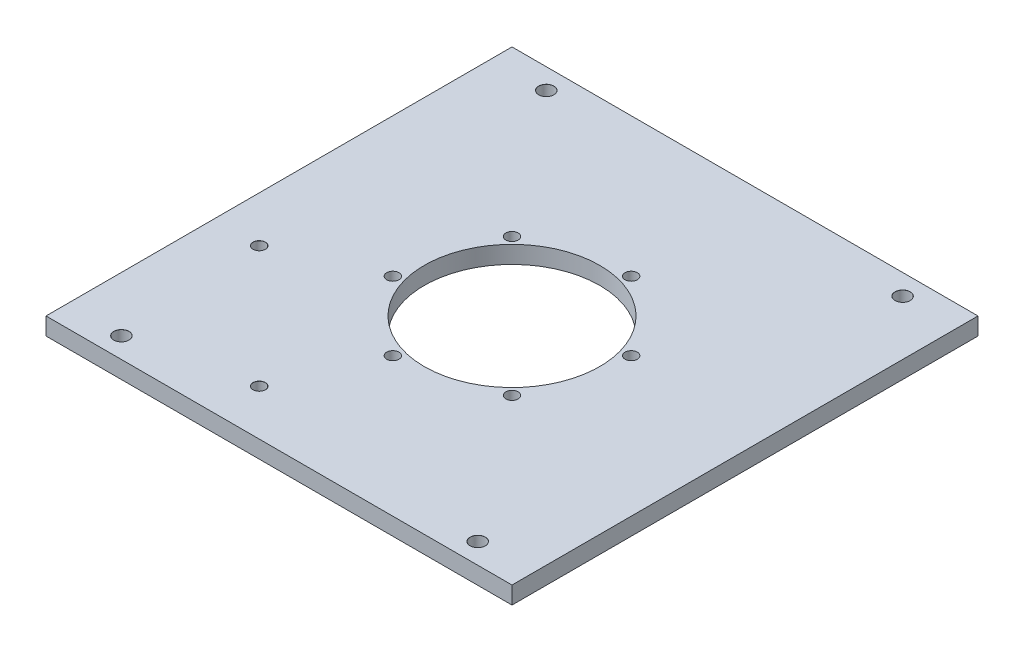
SolidWorks part; units mm, degrees
material "6061 Alloy"
ref_plane "Front Plane" through (0, 0, 0) normal (0, 0, 1) x (1, 0, 0)
ref_plane "Top Plane" through (0, 0, 0) normal (0, 1, 0) x (1, 0, 0)
ref_plane "Right Plane" through (0, 0, 0) normal (1, 0, 0) x (0, 0, -1)
sketch "Sketch1" plane through (0, 0, 0) normal (0, 1, 0) x (1, 0, 0)
  line L1 (-85, -85) -> (85, -85)
  line L2 (-85, -85) -> (-85, 85)
  line L3 (-85, 85) -> (85, 85)
  line L4 (85, -85) -> (85, 85)
  line L5 (-85, -85) -> (85, 85) construction
  line L6 (-85, 85) -> (85, -85) construction
  circle A1 centre (0, 0) radius 39.5
  arc A5 (-25.1023, 25.1023) -> (9.1881, 34.2904) centre (0, 0) cw
  arc A7 (9.1881, 34.2904) -> (-34.2904, -9.1881) centre (0, 0) ccw
  arc A9 (-34.2904, -9.1881) -> (-9.1881, -34.2904) centre (0, 0) ccw
  arc A11 (-9.1881, -34.2904) -> (25.1023, -25.1023) centre (0, 0) ccw
  circle A13 centre (0, 0) radius 32
  arc A14 (25.1023, -25.1023) -> (34.2904, 9.1881) centre (0, 0) ccw
extrude "Boss-Extrude3" add sketch "Sketch1" along normal blind 6.35 contours L1 L4 L3 L2 A1 | A1 A13 region at (-82.5958, 0, 0) region at (-38.3828, 0, 0)
hole_wizard "M4 Clearance Hole2" positions "Sketch6" profile "Sketch7" hole size "M4" standard "ANSI Metric" end condition through all
sketch "Sketch6" plane through (0, 0, 0) normal (0, -1, 0) x (-1, 0, 0)
  point P0 (-9.1881, 34.2904)
  point P3 (25.1023, 25.1023)
  point P6 (34.2904, -9.1881)
  point P9 (9.1881, -34.2904)
  point P12 (-25.1023, -25.1023)
  point P15 (-34.2904, 9.1881)
sketch "Sketch7" plane through (9.1881, 0, -34.2904) normal (1, 0, 0) x (0, 0, -1)
  line L0 (0, 0) -> (0, 6.35)
  line L1 (0, 6.35) -> (2.25, 6.35)
  line L2 (2.25, 6.35) -> (2.25, 0.025)
  line L3 (2.25, 0.025) -> (2.275, 0)
  line L5 (2.275, 0) -> (0, 0)
  line L6 (-2.25, 0.025) -> (-2.275, 0) construction
  line L11 (0, -6.35) -> (0, 107.95) construction
  dimension "Thru Hole Dia." = 4.5
  dimension "Thru Hole Depth" = 6.35
  dimension "Near C'Sink Dia." = 4.55
  dimension "Near C'Sink Angle" = 90
sketch "Sketch13" plane through (0, 6.35, 0) normal (0, 1, 0) x (1, 0, 0)
  line L0 (-85, -85) -> (-46.1091, -46.1091)
  line L1 (-46.1091, -46.1091) -> (-68.3017, -23.9166)
  line L2 (-46.1091, -46.1091) -> (-23.9166, -68.3017)
hole_wizard "M4 Clearance Hole5" positions "Sketch14" profile "Sketch15" hole size "M4" standard "ANSI Metric" end condition through all
sketch "Sketch14" plane through (0, 6.35, 0) normal (0, 1, 0) x (1, 0, 0)
  point P0 (-68.3017, -23.9166)
  point P3 (-23.9166, -68.3017)
sketch "Sketch15" plane through (-68.3017, 6.35, 23.9166) normal (1, 0, 0) x (0, 0, 1)
  line L0 (0, 0) -> (0, 6.35)
  line L1 (0, 6.35) -> (2.25, 6.35)
  line L2 (2.25, 6.35) -> (2.25, 0.025)
  line L3 (2.25, 0.025) -> (2.275, 0)
  line L5 (2.275, 0) -> (0, 0)
  line L6 (-2.25, 0.025) -> (-2.275, 0) construction
  line L11 (0, -6.35) -> (0, 107.95) construction
  dimension "Thru Hole Dia." = 4.5
  dimension "Thru Hole Depth" = 6.35
  dimension "Near C'Sink Dia." = 4.55
  dimension "Near C'Sink Angle" = 90
sketch "Sketch16" plane through (0, 6.35, 0) normal (0, 1, 0) x (1, 0, 0)
  line L0 (-85, -85) -> (-55, -85)
  line L1 (-85, -85) -> (85, -85) construction
  line L2 (-55, -85) -> (-55, -70)
  line L3 (-85, -85) -> (-75, -85)
  line L4 (-75, -85) -> (-75, -70)
  line L5 (-75, -70) -> (-55, -70)
  line L6 (-85, 85) -> (-55, 85)
  line L7 (-85, 85) -> (85, 85) construction
  line L8 (85, 85) -> (55, 85)
  line L9 (85, -85) -> (55, -85)
  line L11 (-55, 85) -> (-75, 85)
  line L12 (-55, 85) -> (-55, 70)
  line L13 (-55, 70) -> (-75, 70)
  line L14 (-75, 85) -> (-75, 70)
  line L15 (55, 85) -> (75, 85)
  line L16 (55, 85) -> (55, 70)
  line L17 (55, 70) -> (75, 70)
  line L18 (75, 85) -> (75, 70)
  line L19 (55, -85) -> (75, -85)
  line L20 (55, -85) -> (55, -70)
  line L21 (55, -70) -> (75, -70)
  line L22 (75, -85) -> (75, -70)
hole_wizard "M5 Clearance Hole1" positions "Sketch19" profile "Sketch20" hole size "M5" standard "ANSI Metric" end condition through all
sketch "Sketch19" plane through (0, 6.35, 0) normal (0, 1, 0) x (1, 0, 0)
  point P0 (-65, -77.5)
sketch "Sketch20" plane through (-65, 6.35, 77.5) normal (1, 0, 0) x (0, 0, 1)
  line L0 (0, 0) -> (0, 6.35)
  line L1 (0, 6.35) -> (2.75, 6.35)
  line L2 (2.75, 6.35) -> (2.75, 0.025)
  line L3 (2.75, 0.025) -> (2.775, 0)
  line L5 (2.775, 0) -> (0, 0)
  line L6 (-2.75, 0.025) -> (-2.775, 0) construction
  line L11 (0, -6.35) -> (0, 107.95) construction
  dimension "Thru Hole Dia." = 5.5
  dimension "Thru Hole Depth" = 6.35
  dimension "Near C'Sink Dia." = 5.55
  dimension "Near C'Sink Angle" = 90
hole_wizard "M5 Clearance Hole2" positions "Sketch21" profile "Sketch22" hole size "M5" standard "ANSI Metric" end condition through all
sketch "Sketch21" plane through (0, 6.35, 0) normal (0, 1, 0) x (1, 0, 0)
  point P0 (-65, 77.5)
  point P2 (65, 77.5)
  point P4 (65, -77.5)
sketch "Sketch22" plane through (-65, 6.35, -77.5) normal (1, 0, 0) x (0, 0, 1)
  line L0 (0, 0) -> (0, 6.35)
  line L1 (0, 6.35) -> (2.75, 6.35)
  line L2 (2.75, 6.35) -> (2.75, 0.025)
  line L3 (2.75, 0.025) -> (2.775, 0)
  line L5 (2.775, 0) -> (0, 0)
  line L6 (-2.75, 0.025) -> (-2.775, 0) construction
  line L11 (0, -6.35) -> (0, 107.95) construction
  dimension "Thru Hole Dia." = 5.5
  dimension "Thru Hole Depth" = 6.35
  dimension "Near C'Sink Dia." = 5.55
  dimension "Near C'Sink Angle" = 90
